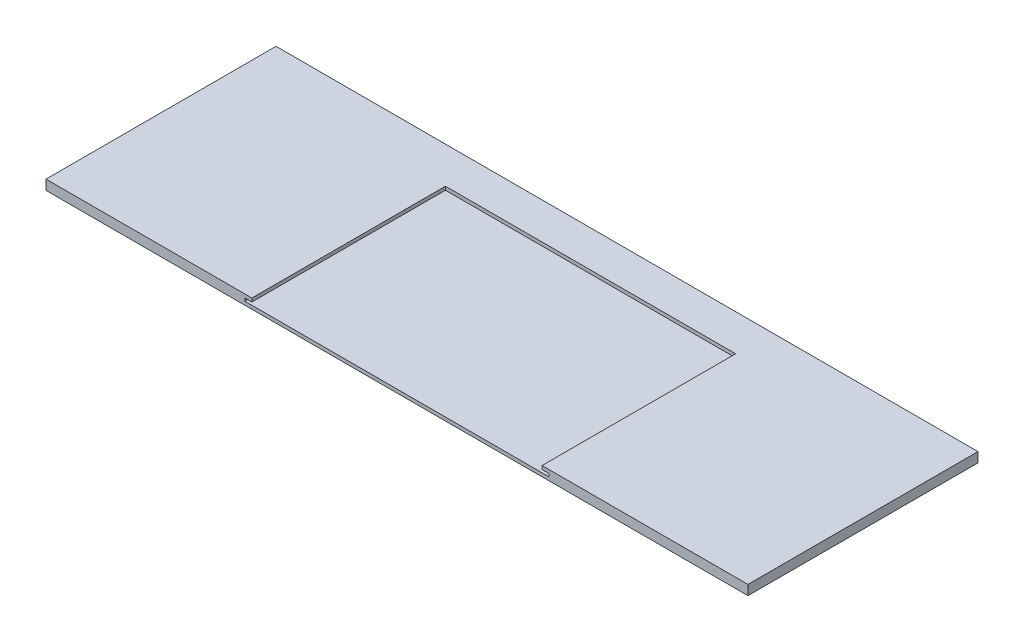
SolidWorks part; units mm, degrees
ref_plane "Front Plane" through (0, 0, 0) normal (0, 0, 1) x (1, 0, 0)
ref_plane "Top Plane" through (0, 0, 0) normal (0, 1, 0) x (1, 0, 0)
ref_plane "Right Plane" through (0, 0, 0) normal (1, 0, 0) x (0, 0, -1)
sketch "Sketch1" plane through (0, 0, 0) normal (0, 1, 0) x (1, 0, 0)
  line L0 (-45.75, -33.1) -> (-45.75, 26.6)
  line L1 (-101, -33.1) -> (101, -33.1)
  line L2 (-101, -33.1) -> (-101, 33.1)
  line L3 (-101, 33.1) -> (101, 33.1)
  line L4 (101, -33.1) -> (101, 33.1)
  line L5 (-101, -33.1) -> (101, 33.1) construction
  line L6 (-101, 33.1) -> (101, -33.1) construction
  line L7 (-43.75, -33.1) -> (43.75, -33.1)
  line L8 (-43.75, -33.1) -> (-43.75, 24.6)
  line L9 (-43.75, 24.6) -> (43.75, 24.6)
  line L10 (43.75, -33.1) -> (43.75, 24.6)
  line L11 (-45.75, 26.6) -> (45.75, 26.6)
  line L12 (45.75, 26.6) -> (45.75, -33.1)
  point P0 (0, 0)
  point P10 (0, 24.6)
  dimension "D1" = 202
  dimension "D2" = 66.2
  dimension "D3" = 87.5
  dimension "D4" = 57.7
  dimension "D5" = 2
  dimension "D6" = 2
  dimension "D7" = 2
extrude "Boss-Extrude1" add sketch "Sketch1" against normal blind 1 contours L11 L12 L1 L4 L3 L2 L0 | L1 L10 L9 L8 | L12 L11 L0 L1 L8 L9 L10 region at (-73.375, 0, 30.9743) region at (-44.6575, 0, 3.25) region at (0, 0, 4.25)
extrude "Boss-Extrude2" add sketch "Sketch1<3>" along normal blind 1.8161 contours L11 L12 L1 L4 L3 L2 L0 | L12 L11 L0 L1 L8 L9 L10 region at (-73.375, 0, 30.9743) region at (-44.6575, 0, 3.25)
sketch "Sketch1<3>" plane through (0, 0, 0) normal (0, 1, 0) x (1, 0, 0) same geometry as "Sketch1"
sketch "Sketch2" plane through (0, 1.8161, 0) normal (0, 1, 0) x (1, 0, 0)
  line L0 (-43.75, -33.1) -> (-41.75, -33.1)
  line L1 (-41.75, -33.1) -> (-41.75, 22.6)
  line L2 (-41.75, 22.6) -> (41.75, 22.6)
  line L3 (41.75, 22.6) -> (41.75, -33.1)
  line L4 (41.75, -33.1) -> (43.75, -33.1)
  line L5 (43.75, -33.1) -> (43.75, 24.6)
  line L6 (43.75, 24.6) -> (-43.75, 24.6)
  line L7 (-43.75, 24.6) -> (-43.75, -33.1)
  dimension "D1" = 2
  dimension "D2" = 2
  dimension "D3" = 2
extrude "Boss-Extrude3" add sketch "Sketch2" against normal blind 1
